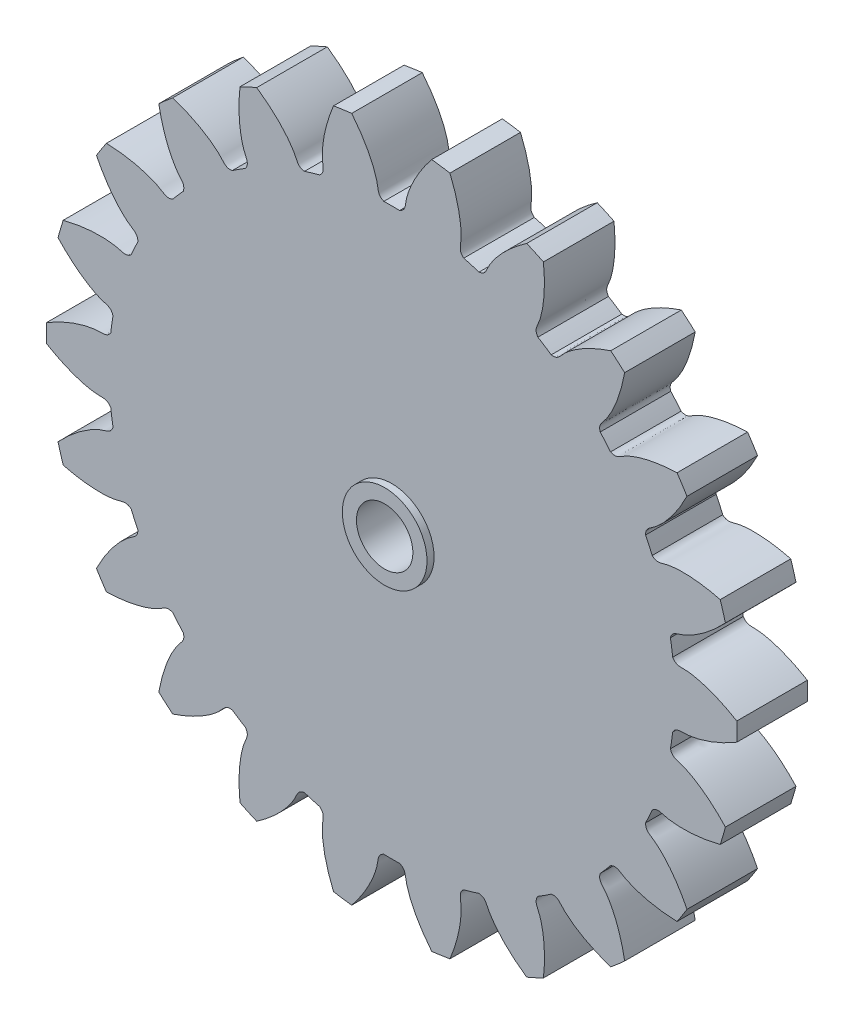
SolidWorks part; units mm, degrees
ref_plane "前视基准面" through (0, 0, 0) normal (0, 0, 1) x (1, 0, 0)
ref_plane "上视基准面" through (0, 0, 0) normal (0, 1, 0) x (1, 0, 0)
ref_plane "右视基准面" through (0, 0, 0) normal (1, 0, 0) x (0, 0, -1)
sketch "草图1" plane through (0, 0, 0) normal (0, 0, 1) x (1, 0, 0)
  circle A0 centre (0, 0) radius 24.4602
extrude "凸台-拉伸1" add sketch "草图1" along normal blind 5
ref_axis "基准轴1" through (0, 0, -0.25) along (0, 0, 1)
sketch "草图2" plane through (0, 0, 0) normal (0, 0, 1) x (1, 0, 0)
  line L0 (0, 0) -> (0, 24.4602) construction
  circle A0 centre (0, 0) radius 24.4602 construction
  arc A1 (0.5626, 20.0321) -> (-0.5626, 20.0321) centre (0, 0) ccw
  arc A2 (6.8859, 27.818) -> (-6.8859, 27.818) centre (0, 0) ccw
  spline S0 degree 3 poles (0.5626, 20.0321) (0.964, 20.2043) (0.954, 20.5243) (1.0135, 20.853) (1.0257, 20.9138) (1.0409, 20.9824) (1.0594, 21.0588) (1.0816, 21.1427) (1.1077, 21.2342) (1.138, 21.333) (1.173, 21.439) (1.2127, 21.5522) (1.2576, 21.6722) (1.308, 21.799) (1.3641, 21.9324) (1.4262, 22.0723) (1.4945, 22.2183) (1.5695, 22.3704) (1.6512, 22.5283) (1.7401, 22.6917) (1.8363, 22.8606) (1.9401, 23.0346) (2.0517, 23.2135) (2.1714, 23.3971) (2.2994, 23.585) (2.436, 23.7772) (2.5812, 23.9732) (2.7354, 24.1728) (2.8988, 24.3757) (3.0715, 24.5816) (3.2537, 24.7903) (3.4456, 25.0014) (3.6474, 25.2146) (3.8592, 25.4297) (4.0812, 25.6462) (4.3135, 25.864) (4.5562, 26.0825) (4.8095, 26.3016) (5.0736, 26.5209) (5.3484, 26.74) (5.6341, 26.9585) (5.9308, 27.1762) (6.3457, 27.4681) (6.6668, 27.6797) (6.8859, 27.818) knots 0 0 0 0 0.086361 0.091598 0.09764 0.104488 0.112142 0.120602 0.129867 0.139938 0.150815 0.162497 0.174985 0.188279 0.202378 0.217283 0.232994 0.249511 0.266833 0.28496 0.303894 0.323633 0.344178 0.365528 0.387684 0.410646 0.434414 0.458987 0.484366 0.51055 0.537541 0.565336 0.593938 0.623345 0.653558 0.684577 0.716401 0.749031 0.782467 0.816708 0.851755 0.887608 0.924266 1 1 1 1
  spline S1 degree 3 poles (-0.5626, 20.0321) (-0.964, 20.2043) (-0.954, 20.5243) (-1.0135, 20.853) (-1.0257, 20.9138) (-1.0409, 20.9824) (-1.0594, 21.0588) (-1.0816, 21.1427) (-1.1077, 21.2342) (-1.138, 21.333) (-1.173, 21.439) (-1.2127, 21.5522) (-1.2576, 21.6722) (-1.308, 21.799) (-1.3641, 21.9324) (-1.4262, 22.0723) (-1.4945, 22.2183) (-1.5695, 22.3704) (-1.6512, 22.5283) (-1.7401, 22.6917) (-1.8363, 22.8606) (-1.9401, 23.0346) (-2.0517, 23.2135) (-2.1714, 23.3971) (-2.2994, 23.585) (-2.436, 23.7772) (-2.5812, 23.9732) (-2.7354, 24.1728) (-2.8988, 24.3757) (-3.0715, 24.5816) (-3.2537, 24.7903) (-3.4456, 25.0014) (-3.6474, 25.2146) (-3.8592, 25.4297) (-4.0812, 25.6462) (-4.3135, 25.864) (-4.5562, 26.0825) (-4.8095, 26.3016) (-5.0736, 26.5209) (-5.3484, 26.74) (-5.6341, 26.9585) (-5.9308, 27.1762) (-6.3457, 27.4681) (-6.6668, 27.6797) (-6.8859, 27.818) knots 0 0 0 0 0.086361 0.091598 0.09764 0.104488 0.112142 0.120602 0.129867 0.139938 0.150815 0.162497 0.174985 0.188279 0.202378 0.217283 0.232994 0.249511 0.266833 0.28496 0.303894 0.323633 0.344178 0.365528 0.387684 0.410646 0.434414 0.458987 0.484366 0.51055 0.537541 0.565336 0.593938 0.623345 0.653558 0.684577 0.716401 0.749031 0.782467 0.816708 0.851755 0.887608 0.924266 1 1 1 1
extrude "切除-拉伸1" cut sketch "草图2" along normal through all
pattern_circular "阵列(圆周)1" count 22 over 360 about axis through (0, 0, -0.25) along (0, 0, 1) of "切除-拉伸1"
sketch "草图3" plane through (0, 0, 0) normal (0, 0, 1) x (1, 0, 0)
  circle A0 centre (0, 0) radius 22 construction
  dimension "Dn" = 44
sketch "草图4" plane through (0, 0, 5) normal (0, 0, 1) x (1, 0, 0)
  circle A0 centre (0, 0) radius 3
  dimension "D1" = 6
extrude "凸台-拉伸2" add sketch "草图4" along normal blind 0.5
sketch "草图5" plane through (0, 0, 5.5) normal (0, 0, 1) x (1, 0, 0)
  circle A0 centre (0, 0) radius 2
  dimension "D1" = 4
extrude "切除-拉伸2" cut sketch "草图5" against normal through all
chamfer "倒角1" distance 0.5 angle 45 1 edges at (2, 0, 0)
